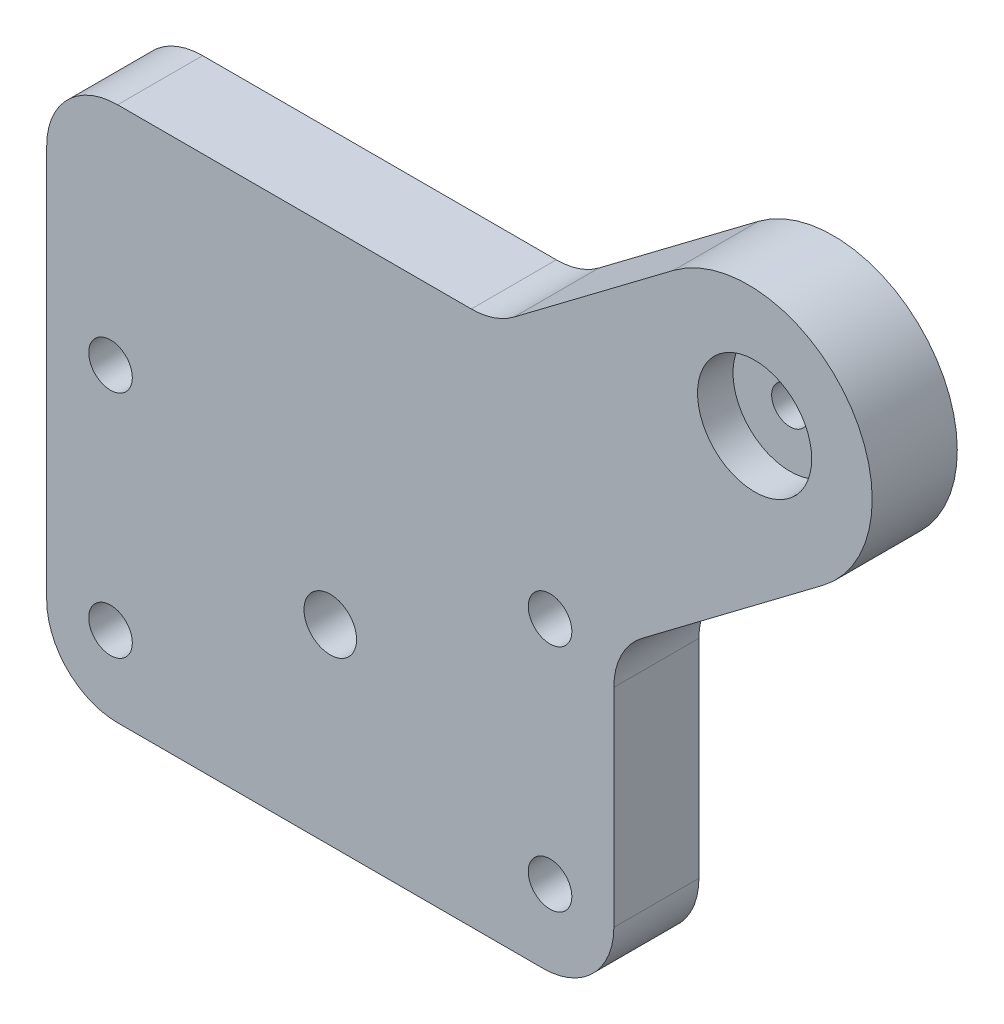
SolidWorks part; units mm, degrees
ref_plane "Front Plane" through (0, 0, 0) normal (0, 0, 1) x (1, 0, 0)
ref_plane "Top Plane" through (0, 0, 0) normal (0, 1, 0) x (1, 0, 0)
ref_plane "Right Plane" through (0, 0, 0) normal (1, 0, 0) x (0, 0, -1)
ref_plane "Plane1" through (0, 0, 26) normal (0, 0, 1) x (1, 0, 0)
sketch "Sketch1" plane through (0, 0, 26) normal (0, 0, 1) x (1, 0, 0)
  line L0 (48.4156, 256.4761) -> (23.2334, 237.5)
  line L1 (23.2334, 237.5) -> (-40, 237.5)
  line L2 (-40, 237.5) -> (-40, 162)
  line L3 (-40, 162) -> (40, 162)
  line L4 (40, 162) -> (40, 206.3098)
  line L5 (40, 206.3098) -> (69.4791, 228.5239)
  arc A0 (69.4791, 228.5239) -> (48.4156, 256.4761) centre (58.9473, 242.5) ccw
  circle A1 centre (0, 189) radius 3.7067
extrude "Boss-Extrude1" add sketch "Sketch1" against normal blind 12
hole_wizard "#12 Clearance Hole1" positions "Sketch3" profile "Sketch2" hole size "#12" standard "ANSI Inch"
sketch "Sketch3" plane through (0, 0, 26) normal (0, 0, 1) x (1, 0, 0)
  point P0 (31, 172.8)
  point P1 (-31, 205.2)
  point P2 (-31, 172.8)
  point P3 (31, 205.2)
sketch "Sketch2" plane through (31, 172.8, 26) normal (1, 0, 0) x (0, -1, 0)
  line L0 (0, 0) -> (0, 12)
  line L1 (0, 12) -> (3.075, 12)
  line L2 (3.075, 12) -> (3.075, 0)
  line L5 (3.075, 0) -> (0, 0)
  line L11 (0, -6.35) -> (0, 107.95) construction
  dimension "Thru Hole Dia." = 6.15
  dimension "Thru Hole Depth" = 12
fillet "Fillet1" radius 10 5 edges at (40, 206.3098, 20) (-40, 237.5, 20) (23.2334, 237.5, 20) (-40, 162, 20) (40, 162, 20) tangent propagation no
sketch "Sketch6" plane through (0, 0, 26) normal (0, 0, 1) x (1, 0, 0)
  line L0 (43.9818, 209.3103) -> (69.4791, 228.5239) construction
  line L1 (48.4156, 256.4761) -> (25.9056, 239.5136) construction
  line L2 (37.1606, 247.9949) -> (58.2241, 220.0426) construction
  line L3 (47.6923, 234.0188) -> (59.8577, 243.186) construction
  circle A0 centre (59.8577, 243.186) radius 8.05
  arc A2 (69.4791, 228.5239) -> (48.4156, 256.4761) centre (58.9473, 242.5) ccw construction
  circle A3 centre (59.8577, 243.186) radius 2.6
  dimension "D1" = 10.59
  dimension "D2" = 16.1
extrude "Cut-Extrude1" cut sketch "Sketch6" against normal blind 5
extrude "Cut-Extrude2" cut sketch "Sketch6<2>" against normal through all contours A3 region at (59.8577, 243.186, 26)
sketch "Sketch6<2>" plane through (0, 0, 26) normal (0, 0, 1) x (1, 0, 0) same geometry as "Sketch6"
